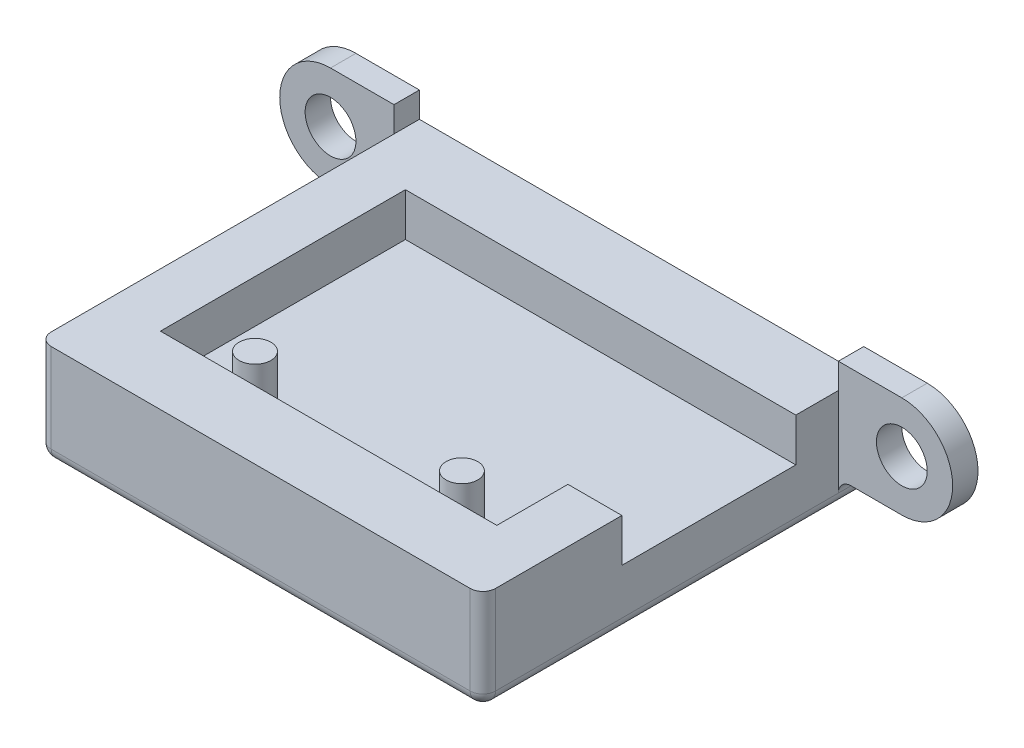
SolidWorks part; units mm, degrees
ref_plane "Alzado" through (0, 0, 0) normal (0, 0, 1) x (1, 0, 0)
ref_plane "Planta" through (0, 0, 0) normal (0, 1, 0) x (1, 0, 0)
ref_plane "Vista lateral" through (0, 0, 0) normal (1, 0, 0) x (0, 0, -1)
sketch "Croquis1" plane through (0, 0, 0) normal (0, 1, 0) x (1, 0, 0)
  line L1 (-17.5, 15) -> (17.5, 15)
  line L2 (-17.5, 15) -> (-17.5, -15)
  line L3 (-17.5, -15) -> (17.5, -15)
  line L4 (17.5, 15) -> (17.5, -15)
  line L5 (-17.5, 15) -> (17.5, -15) construction
  line L6 (-17.5, -15) -> (17.5, 15) construction
  point P0 (0, 0)
  dimension "D1" = 30
  dimension "D2" = 35
extrude "Saliente-Extruir1" add sketch "Croquis1" along normal blind 8
sketch "Croquis2" plane through (0, 8, 0) normal (0, 1, 0) x (1, 0, 0)
  line L0 (13.25, 9.65) -> (17.5, 9.65)
  line L1 (-13.25, 9.65) -> (13.25, 9.65)
  line L2 (-13.25, 9.65) -> (-13.25, -9.65)
  line L3 (-13.25, -9.65) -> (13.25, -9.65)
  line L4 (13.25, -4.05) -> (13.25, -9.65)
  line L5 (-13.25, 9.65) -> (13.25, -9.65) construction
  line L6 (-13.25, -9.65) -> (13.25, 9.65) construction
  line L7 (17.5, -15) -> (17.5, 15) construction
  line L8 (17.5, 9.65) -> (17.5, -4.05)
  line L9 (17.5, -4.05) -> (13.25, -4.05)
  line L10 (0, -9.65) -> (0, -7.3) construction
  line L11 (-8.15, -7.3) -> (8.15, -7.3) construction
  circle A0 centre (-8.15, -7.3) radius 1.25
  circle A1 centre (8.15, -7.3) radius 1.25
  point P0 (0, 0)
  point P15 (0, -7.3)
  dimension "D5" = 2.5
  dimension "D1" = 26.5
  dimension "D2" = 19.3
  dimension "D3" = 13.7
  dimension "D4" = 16.3
  dimension "D6" = 2.35
extrude "Cortar-Extruir2" cut sketch "Croquis2" against normal blind 3.4
sketch "Croquis3" plane through (0, 0, -15) normal (0, 0, -1) x (-1, 0, 0)
  line L8 (0, -4.9839) -> (0, 11.9794) construction
  line L9 (-17.5, 0) -> (-17.5, 2) construction
  line L10 (-17.5, 8) -> (-17.5, 0) construction
  line L11 (-17.5, 2) -> (-17.5, 10)
  line L12 (-17.5, 2) -> (-22.5, 2)
  line L13 (-17.5, 10) -> (-22.5, 10)
  line L15 (17.5, 10) -> (22.5, 10)
  line L16 (17.5, 2) -> (17.5, 10)
  line L17 (17.5, 2) -> (22.5, 2)
  arc A4 (-22.5, 10) -> (-22.5, 2) centre (-22.5, 6) ccw
  circle A5 centre (-22.5, 6) radius 2
  arc A6 (22.5, 10) -> (22.5, 2) centre (22.5, 6) cw
  circle A7 centre (22.5, 6) radius 2
  dimension "D3" = 5
  dimension "D4" = 4
  dimension "D1" = 2
  dimension "D2" = 8
extrude "Saliente-Extruir2" add sketch "Croquis3" against normal blind 2
fillet "Redondeo1" radius 1 7 edges at (17.5, 2, -14) (17.5, 0, 0) (0, 0, 15) (-17.5, 0, 0) (-17.5, 2, -14) (-17.5, 4, 15) (17.5, 4, 15)
